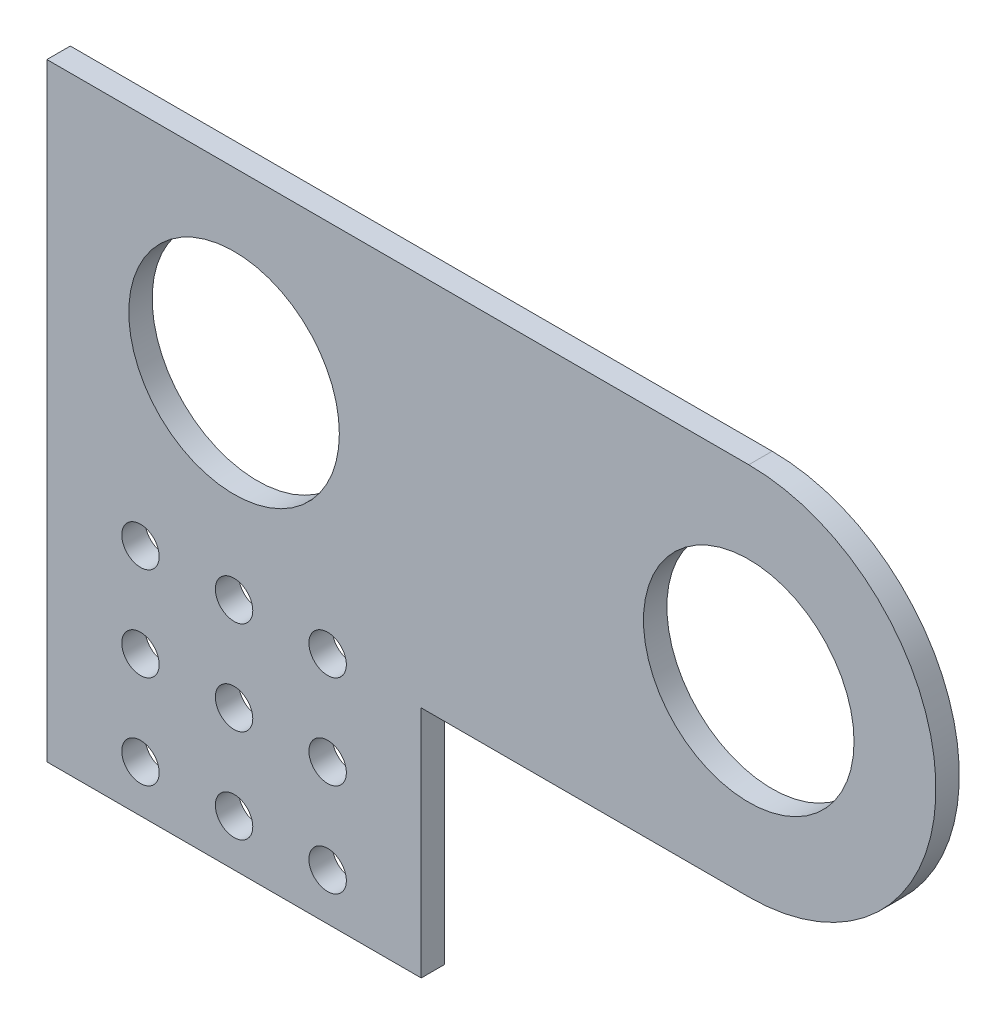
SolidWorks part; units mm, degrees
ref_plane "Front Plane" through (0, 0, 0) normal (0, 0, 1) x (1, 0, 0)
ref_plane "Top Plane" through (0, 0, 0) normal (0, 1, 0) x (1, 0, 0)
ref_plane "Right Plane" through (0, 0, 0) normal (1, 0, 0) x (0, 0, -1)
sketch "Sketch1" plane through (0, 0, 0) normal (0, 0, 1) x (1, 0, 0)
  line L0 (1.1768, -201.4853) -> (1.1768, -150.6853)
  line L1 (1.1768, -150.6853) -> (96.4268, -150.6853)
  line L2 (96.4268, -201.4853) -> (51.9768, -201.4853)
  line L3 (51.9768, -201.4853) -> (51.9768, -233.2353)
  line L4 (51.9768, -233.2353) -> (1.1768, -233.2353)
  line L5 (1.1768, -233.2353) -> (1.1768, -201.4853)
  line L6 (11.3368, -150.6853) -> (1.1768, -150.6853) construction
  line L8 (1.1768, -201.4853) -> (96.4268, -201.4853) construction
  arc A0 (96.4268, -150.6853) -> (96.4268, -201.4853) centre (96.4268, -176.0853) cw
  circle A1 centre (13.8768, -201.4853) radius 2.54
  circle A2 centre (26.5768, -201.4853) radius 2.54
  circle A3 centre (39.2768, -214.1853) radius 2.54
  circle A4 centre (26.5768, -214.1853) radius 2.54
  circle A5 centre (39.2768, -201.4853) radius 2.54
  circle A6 centre (26.5768, -226.8853) radius 2.54
  circle A7 centre (39.2768, -226.8853) radius 2.54
  circle A8 centre (13.8768, -214.1853) radius 2.54
  circle A9 centre (13.8768, -226.8853) radius 2.54
  circle A10 centre (96.4268, -176.0853) radius 14.2875
  arc A11 (40.8458, -174.0878) -> (12.3078, -174.0878) centre (26.5768, -174.8153) ccw construction
  arc A12 (40.8458, -174.0878) -> (12.3078, -174.0878) centre (26.5768, -174.8153) ccw construction
  circle A13 centre (13.8768, -226.8853) radius 2.54 construction
  circle A14 centre (13.8768, -226.8853) radius 2.54 construction
  circle A15 centre (26.5768, -174.8153) radius 14.2875
  point P27 (-0.0988, -43.4457)
  point P30 (7.3331, -57.8725)
  point P38 (0, 0)
  point P39 (0, 0)
  point P40 (12.7, -50.8)
  point P42 (25.4, -63.5)
  point P43 (25.4, -38.1)
  point P46 (38.1, -50.8)
  point P48 (25.4, -50.8)
  point P50 (38.1, -38.1)
  point P52 (0, 0)
  point P53 (209.6412, 9.9444)
  point P54 (0, 0)
  point P55 (0, 0)
  point P56 (0, 0)
  point P57 (25.4, -50.8)
  point P58 (0, 0)
  dimension "D10" = 28.575
  dimension "D1" = 50.8
  dimension "D2" = 95.25
  dimension "D4" = 12.7
  dimension "D8" = 12.7
  dimension "D11" = 50.8
  dimension "D12" = 31.75
  dimension "D13" = 50.8
extrude "Boss-Extrude1" add sketch "Sketch1" along normal blind 3.175
